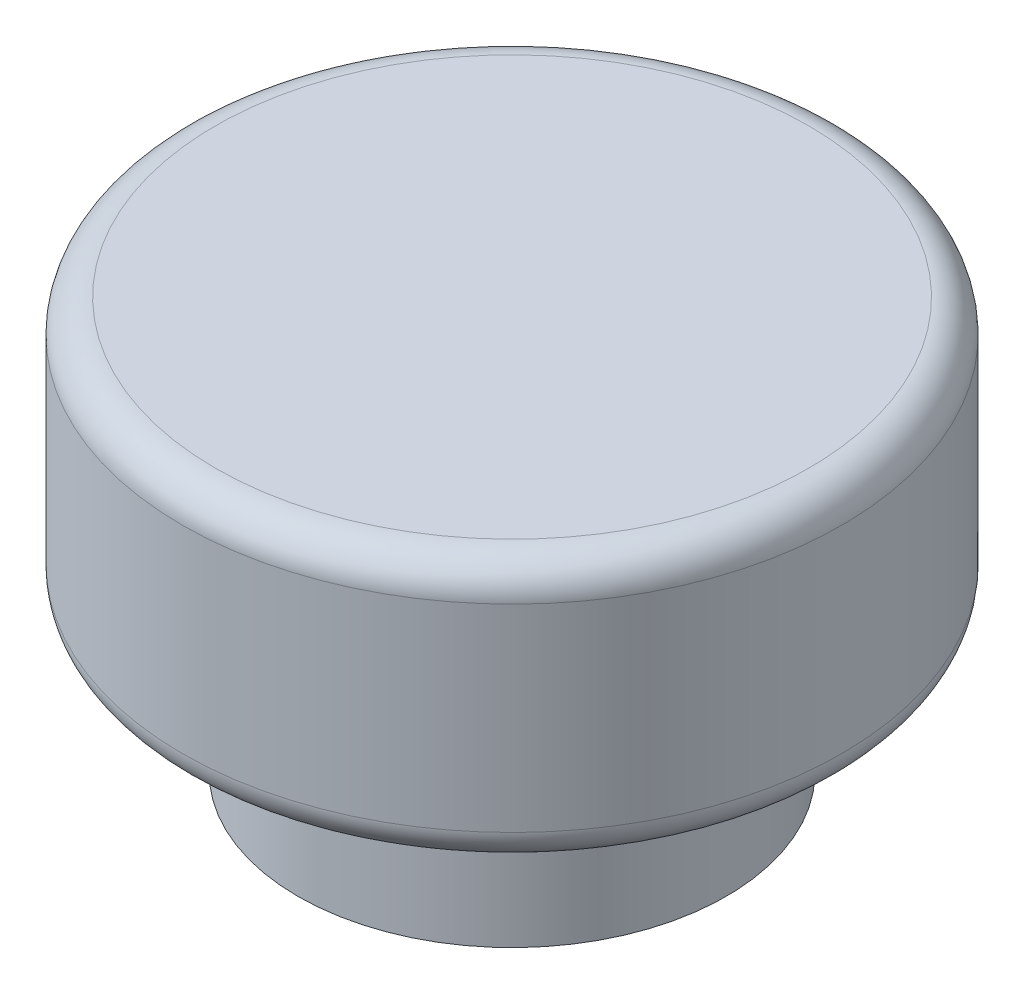
SolidWorks part; units mm, degrees
ref_plane "Front Plane" through (0, 0, 0) normal (0, 0, 1) x (1, 0, 0)
ref_plane "Top Plane" through (0, 0, 0) normal (0, 1, 0) x (1, 0, 0)
ref_plane "Right Plane" through (0, 0, 0) normal (1, 0, 0) x (0, 0, -1)
sketch "Sketch1" plane through (0, 0, 0) normal (0, 1, 0) x (1, 0, 0)
  line L1 (0.6582, 0) -> (0.3291, 0.57)
  line L2 (0.3291, 0.57) -> (-0.3291, 0.57)
  line L3 (-0.3291, 0.57) -> (-0.6582, 0)
  line L4 (-0.6582, 0) -> (-0.3291, -0.57)
  line L5 (-0.3291, -0.57) -> (0.3291, -0.57)
  line L6 (0.3291, -0.57) -> (0.6582, 0)
  circle A0 centre (0, 0) radius 0.57 construction
extrude "Boss-Extrude1" add sketch "Sketch1" along normal blind 1.75
sketch "Sketch2" plane through (0, 1.75, 0) normal (0, 1, 0) x (1, 0, 0)
  line L0 (0, 0) -> (0, -0.1986)
  line L1 (0.6582, 0) -> (0.3291, 0.57)
  line L2 (0.3291, 0.57) -> (-0.3291, 0.57)
  line L3 (-0.3291, 0.57) -> (-0.6582, 0)
  line L4 (-0.6582, 0) -> (-0.3291, -0.57)
  line L5 (-0.3291, -0.57) -> (0.3291, -0.57)
  line L6 (0.3291, -0.57) -> (0.6582, 0)
  line L7 (4.375, 0) -> (-2.1875, 3.7889) construction
  line L8 (-2.1875, 3.7889) -> (-2.1875, -3.7889) construction
  line L9 (-2.1875, -3.7889) -> (4.375, 0) construction
  line L10 (0, -0.1986) -> (0, 0.1978)
  line L11 (0, 0.1978) -> (4.375, 0)
  line L12 (4.375, 0) -> (0, -0.1986)
  circle A0 centre (0, 0) radius 0.57 construction
  circle A1 centre (0, 0) radius 4.375 construction
  line M2 (0.6582, 0) -> (0.3291, 0.57)
extrude "Boss-Extrude2" add sketch "Sketch2" along normal blind 0.5 contours L12 L11 L6 M2 | L12 L6 L11 L10 L0 M2 region at (0.2973, 1.75, 0.0004) region at (1.8638, 1.75, 0.0003)
sketch "Sketch3" plane through (0, 1.75, 0) normal (0, 1, 0) x (1, 0, 0)
  line L0 (0.6582, 0) -> (0.3291, 0.57)
  line L1 (-0.6582, 0) -> (-0.3291, -0.57)
  line L2 (-0.3291, -0.57) -> (0.3291, -0.57)
  line L3 (0.3291, -0.57) -> (0.6582, 0)
  line L4 (0.3291, 0.57) -> (-0.3291, 0.57)
  line L5 (-0.3291, 0.57) -> (-0.6582, 0)
  circle A0 centre (0, 0) radius 0.6582 construction
extrude "Boss-Extrude5" add sketch "Sketch3" along normal blind 3.5
sketch "Sketch4" plane through (0, 5.25, 0) normal (0, 1, 0) x (1, 0, 0)
  circle A0 centre (0, 0) radius 3.5
extrude "Boss-Extrude7" add sketch "Sketch4" along normal blind 2
sketch "Sketch11" plane through (0, 1.75, 0) normal (0, -1, 0) x (-1, 0, 0)
  circle A0 centre (0, 0) radius 4.5054
  circle A1 centre (0, 0) radius 3.5
extrude "Cut-Extrude3" cut sketch "Sketch11" against normal blind 2
sketch "Sketch12" plane through (0, 0, 0) normal (0, -1, 0) x (-1, 0, 0)
  circle A0 centre (0, 0) radius 3.5
extrude "Cut-Extrude4" cut sketch "Sketch12" against normal blind 3
sketch "Sketch16" plane through (0, 3, 0) normal (0, -1, 0) x (-1, 0, 0)
  line L0 (1.1, 0) -> (-1.1, 0)
  line L1 (-1.1, 0) -> (-0.55, -0.9526)
  line L2 (-0.55, -0.9526) -> (0.55, -0.9526)
  line L3 (0.55, -0.9526) -> (1.1, 0)
  line L4 (1.1, 0) -> (0.55, 0.9526)
  line L5 (0.55, 0.9526) -> (-0.55, 0.9526)
  line L6 (-0.55, 0.9526) -> (-1.1, 0)
  circle A0 centre (0, 0) radius 0.9526 construction
  line M1 (-0.6582, 0) -> (-0.3291, -0.57)
  line M2 (-0.3291, -0.57) -> (0.3291, -0.57)
  line M3 (0.3291, -0.57) -> (0.6582, 0)
  line M4 (0.6582, 0) -> (0.3291, 0.57)
  line M5 (0.3291, 0.57) -> (-0.3291, 0.57)
  line M6 (-0.3291, 0.57) -> (-0.6582, 0)
  dimension "D1" = 2.2
extrude "Boss-Extrude8" add sketch "Sketch16" against normal blind 2.5 contours L2 L3 L0 L1 M3 M2 M1 | L5 L6 L0 L4 M6 M5 M4 | L0 M4 M5 M6 | L0 M3 M1 M2 region at (-0.8042, 3, 0.4643) region at (-0.8791, 3, -0.024) region at (0, 3, 0.2533) region at (0, 3, -0.2533)
chamfer "Chamfer1" distance 0.5 angle 30 6 edges at (0, 5.25, 0.9526) (-0.825, 5.25, 0.4763) (-0.825, 5.25, -0.4763) (0, 5.25, -0.9526) (0.825, 5.25, -0.4763) (0.825, 5.25, 0.4763) first distance on face at (0, 4.125, 0.9526) first distance on face at (-0.825, 4.125, 0.4763) first distance on face at (-0.825, 4.125, -0.4763) first distance on face at (0, 4.125, -0.9526) first distance on face at (0.825, 4.125, -0.4763) first distance on face at (0.825, 4.125, 0.4763)
sketch "Sketch17" plane through (0, 3, 0) normal (0, -1, 0) x (-1, 0, 0)
  line L1 (-2.9959, 0) -> (-1.498, -2.5945)
  line L2 (-1.498, -2.5945) -> (1.498, -2.5945)
  line L3 (1.498, -2.5945) -> (2.9959, 0)
  line L4 (2.9959, 0) -> (1.498, 2.5945)
  line L5 (1.498, 2.5945) -> (-1.498, 2.5945)
  line L6 (-1.498, 2.5945) -> (-2.9959, 0)
  circle A0 centre (0, 0) radius 2.5945 construction
  circle A1 centre (0, 0) radius 3.25
extrude "Boss-Extrude9" add sketch "Sketch17" against normal blind 3
sketch "Sketch18" plane through (0, 3, 0) normal (0, -1, 0) x (-1, 0, 0)
  circle A0 centre (0, 0) radius 1.7681
extrude "Cut-Extrude8" cut sketch "Sketch18" against normal blind 2.25
sketch "Sketch20" plane through (0, 7.25, 0) normal (0, 1, 0) x (1, 0, 0)
  circle A0 centre (0, 0) radius 5
extrude "Boss-Extrude10" add sketch "Sketch20" against normal blind 2
sketch "Sketch21" plane through (0, 7.25, 0) normal (0, 1, 0) x (1, 0, 0)
  circle A0 centre (0, 0) radius 5
extrude "Boss-Extrude11" add sketch "Sketch21" along normal blind 2
fillet "Fillet1" radius 0.5 2 edges at (0, 5.25, 5) (0, 9.25, 5)
fillet "Fillet2" radius 0.5 1 edges at (0, 5.25, 3.25)
